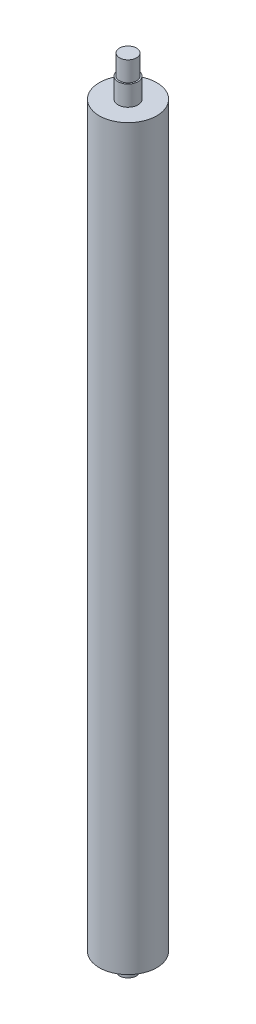
SolidWorks part; units mm, degrees
material "Stainless Steel (ferritic)"
ref_plane "Front Plane" through (0, 0, 0) normal (0, 0, 1) x (1, 0, 0)
ref_plane "Top Plane" through (0, 0, 0) normal (0, 1, 0) x (1, 0, 0)
ref_plane "Right Plane" through (0, 0, 0) normal (1, 0, 0) x (0, 0, -1)
sketch "Sketch1" plane through (0, 0, 0) normal (0, 1, 0) x (1, 0, 0)
  circle A0 centre (0, 0) radius 3.965
  circle A1 centre (0, 0) radius 3.45
  circle A2 centre (0, 0) radius 2.95
  dimension "D1" = 7.93
  dimension "D2" = 6.9
  dimension "D3" = 5.9
extrude "Boss-Extrude1" add sketch "Sketch1" along normal blind 6.8 contours A1 | A0
extrude "Boss-Extrude2" add sketch "Sketch1<3>" along normal blind 13.8 contours A1 A2 region at (-3.3524, 0, 0)
sketch "Sketch1<3>" plane through (0, 0, 0) normal (0, 1, 0) x (1, 0, 0) same geometry as "Sketch1"
extrude "Boss-Extrude3" add sketch "Sketch1<4>" along normal blind 20.75 contours A2 region at (0, 0, 0)
sketch "Sketch1<4>" plane through (0, 0, 0) normal (0, 1, 0) x (1, 0, 0) same geometry as "Sketch1"
extrude "Boss-Extrude4" add sketch "Sketch1<5>" against normal blind 250 contours A2 | A1 A2 | A0 A1 region at (-3.8529, 0, 0) region at (-3.3524, 0, 0) region at (0, 0, 0)
sketch "Sketch1<5>" plane through (0, 0, 0) normal (0, 1, 0) x (1, 0, 0) same geometry as "Sketch1"
extrude "Boss-Extrude5" add sketch "Sketch1<6>" against normal blind 256 contours A2 region at (0, 0, 0)
sketch "Sketch1<6>" plane through (0, 0, 0) normal (0, 1, 0) x (1, 0, 0) same geometry as "Sketch1"
sketch "Sketch2" plane through (0, -250, 0) normal (0, -1, 0) x (1, 0, 0)
  circle A0 centre (0, 0) radius 10
  dimension "D1" = 20
extrude "Boss-Extrude6" add sketch "Sketch2" against normal up to surface (256.8 mm away) up to face at (0, 6.8, 3.965)
